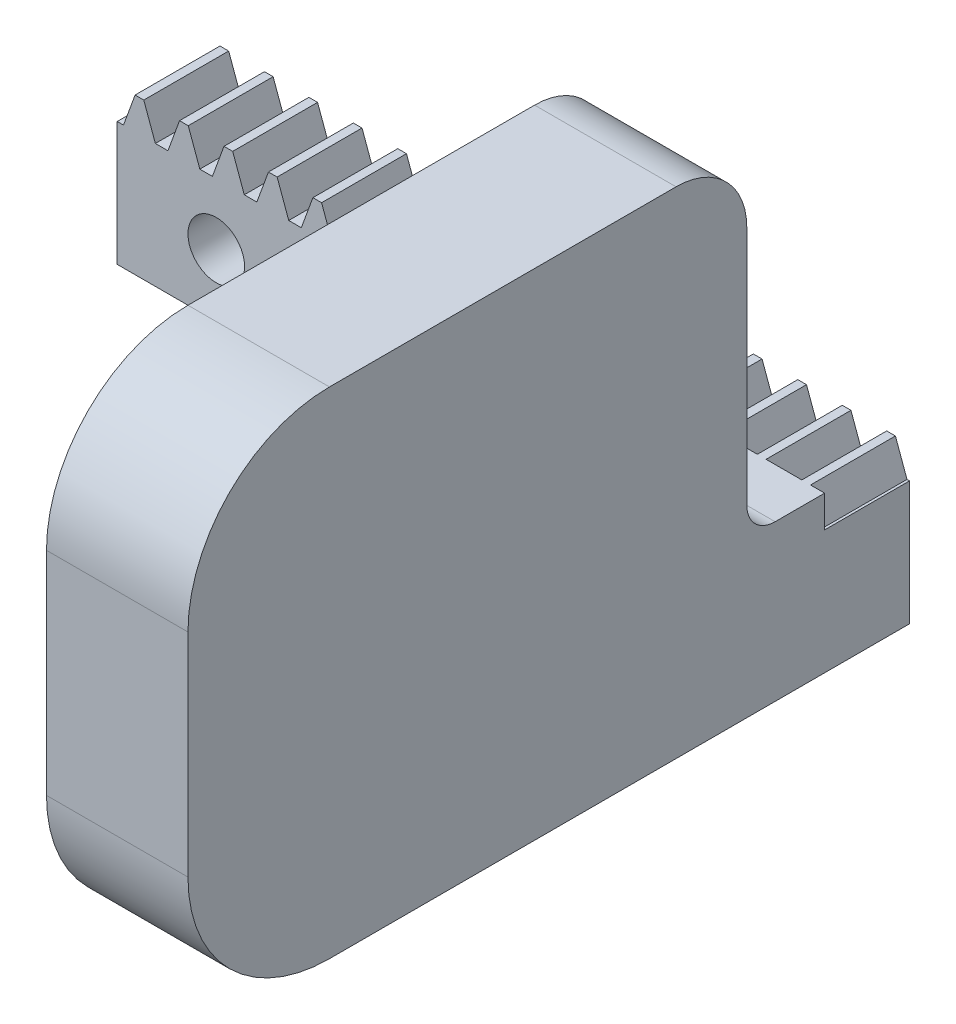
SolidWorks part; units mm, degrees
extrude "Blank" add sketch "BlankSke" against normal blind 6
sketch "BlankSke" plane through (0, 0, 0) normal (0, 0, 1) x (1, 0, 0)
  line L1 (0, 0) -> (50, 0)
  line L2 (0, 0) -> (0, 11)
  line L3 (0, 11) -> (50, 11)
  line L4 (50, 0) -> (50, 11)
  dimension "Length" = 50
ref_plane "Plane1" through (0, 0, 0) normal (0, 0, 1) x (1, 0, 0)
ref_plane "Plane2" through (0, 0, 0) normal (0, 1, 0) x (1, 0, 0)
ref_plane "Plane3" through (0, 0, 0) normal (1, 0, 0) x (0, 0, -1)
sketch "HoldingSke" plane through (0, 0, 0) normal (0, 1, 0) x (1, 0, 0)
  line L0 (0, 0) -> (0.1392, 0.9903)
  line L1 (-15, 0) -> (100, 0) construction
  line L2 (0, 0) -> (-2.1039, 2.3779)
  line L3 (0, 0) -> (-11.863, 4.5341)
  line L4 (0, 0) -> (8.2587, 2.5249)
  line L5 (0, 0) -> (-23.7986, -8.8762)
  line L6 (0, 0) -> (-10.5278, -7.1032)
  line L9 (-71.009, 38.7566) -> (-24.0243, 55.8576)
  line L10 (-76.2, 3.3779) -> (-66.2, 3.3779)
  line L11 (0, 0) -> (-6, 0)
  line L12 (-76.2, 101.6) -> (-76.162, 101.6)
  line L13 (24.9733, 27.94) -> (52.9518, 28.4284)
  line L14 (24.9733, 27.94) -> (24.9743, 27.94)
  line L15 (24.9733, 27.94) -> (100.4006, 29.5858)
  circle A0 centre (0, 0) radius 19.05
  circle A1 centre (0, 0) radius 5
  circle A2 centre (0, 0) radius 12.7
  dimension "Num_teeth" = 17
  dimension "Width" = 6
  dimension "Length" = 50
  dimension "Pitch_height" = 10
sketch "TooCutSkeIll" plane through (0, 0, 0) normal (0, 0, 1) x (1, 0, 0)
  line L0 (-1.2538, 10.9737) -> (-0.5045, 8.9152)
  line L1 (-0.2687, 8.75) -> (0.2687, 8.75)
  line L2 (0.5045, 8.9152) -> (1.2538, 10.9737)
  line L3 (50, 11) -> (0, 11) construction
  line L4 (0, 0) -> (0, 64.897) construction
  line L5 (-13.208, 10) -> (12.954, 10) construction
  line L6 (0, 0) -> (50, 0) construction
  line L7 (0.8994, 10) -> (0.8994, 48.7463) construction
  line L8 (-0.8994, 10) -> (-0.8994, 48.7463) construction
  line L9 (1.2914, 11) -> (1.2914, 11.0254)
  line L10 (-1.2914, 11) -> (-1.2914, 11.0254)
  line L11 (-1.2914, 11.0254) -> (1.2914, 11.0254)
  arc A0 (0.2687, 8.75) -> (0.5045, 8.9152) centre (0.2687, 9.001) ccw
  arc A1 (-0.5045, 8.9152) -> (-0.2687, 8.75) centre (-0.2687, 9.001) ccw
  arc A2 (1.2914, 11) -> (1.2538, 10.9737) centre (1.2914, 10.96) ccw
  arc A3 (-1.2538, 10.9737) -> (-1.2914, 11) centre (-1.2914, 10.96) ccw
  dimension "Addendum_plus" = 1.0254
  dimension "Pitch_height" = 10
  dimension "Pressure_angle" = 20
  dimension "Gap_width" = 1.7988
  dimension "Dedendum" = 1.25
extrude "ToothCutIll" [suppressed] cut sketch "TooCutSkeIll" against normal through all
sketch "TooCutSkeSim" plane through (0, 0, 0) normal (0, 0, 1) x (1, 0, 0)
  line L0 (0.4444, 8.75) -> (-0.4444, 8.75)
  line L1 (1.2726, 11.0254) -> (0.4444, 8.75)
  line L2 (0, 17.4625) -> (0, 53.467) construction
  line L3 (1.2726, 11.0254) -> (-1.2726, 11.0254)
  line L6 (-1.2726, 11.0254) -> (-0.4444, 8.75)
  line L9 (-0.8994, 10) -> (0.8994, 10) construction
  line L10 (0, 0) -> (50, 0) construction
  line L11 (0.8994, 10) -> (0.8994, 53.467) construction
  line L12 (-0.8994, 10) -> (-0.8994, 53.467) construction
  dimension "Addendum_plus" = 1.0254
  dimension "Pitch_height" = 10
  dimension "Pressure_angle" = 20
  dimension "Gap_width" = 1.7988
  dimension "Dedendum" = 1.25
extrude "ToothCutSim" cut sketch "TooCutSkeSim" against normal through all
pattern_linear "TeethCuts" count 17 spacing 3.1416 along (1, 0, 0) of "ToothCutIll", "ToothCutSim"
sketch "Sketch1" plane through (0, 0, 0) normal (0, 0, 1) x (1, 0, 0)
  line L1 (50, 0) -> (40, 0)
  line L2 (50, 0) -> (50, 35)
  line L3 (50, 35) -> (40, 35)
  line L4 (40, 0) -> (40, 35)
  dimension "D1" = 35
  dimension "D2" = 10
extrude "Boss-Extrude1" add sketch "Sketch1" along normal blind 45
fillet "Fillet1" radius 10 2 edges at (45, 0, 45) (45, 35, 45)
sketch "Sketch2" plane through (0, 0, 0) normal (0, 0, 1) x (1, 0, 0)
  line L0 (0, 8.75) -> (0, 0) construction
  line L1 (0, 4.375) -> (9, 4.375) construction
  line L2 (7, 8.1846) -> (7, 0) construction
  line L3 (0, 0) -> (40, 0) construction
  line L4 (40, 9.8387) -> (40, 0) construction
  line L5 (39.5773, 11) -> (38.9625, 11) construction
  circle A0 centre (7, 4.375) radius 2
  circle A1 centre (32, 4.375) radius 2
  dimension "D1" = 7
  dimension "D3" = 4
  dimension "D4" = 0.4227
  dimension "D2" = 25
  dimension "D5" = 1.1613
  dimension "D6" = 6.625
extrude "Cut-Extrude1" cut sketch "Sketch2" against normal blind 25
ref_axis "Axis1" through (50, 0, -6) along (-1, 0, 0)
sketch "Sketch3" plane through (0, 0, -6) normal (0, 0, -1) x (-1, 0, 0)
  circle A2 centre (-7, 4.375) radius 2 construction
  circle A3 centre (-32, 4.375) radius 2 construction
  circle A4 centre (-7, 4.375) radius 2
  circle A5 centre (-32, 4.375) radius 2
  circle A6 centre (-32, 4.375) radius 3
  circle A7 centre (-7, 4.375) radius 3
  dimension "D1" = 1
extrude "Boss-Extrude2" [suppressed] add sketch "Sketch3" along normal blind 4
sketch "Sketch4" plane through (40, 0, 0) normal (-1, 0, 0) x (0, 0, 1)
  line L1 (0, 11) -> (5.5, 11)
  line L2 (0, 11) -> (0, 41)
  line L3 (0, 41) -> (5.5, 41)
  line L4 (5.5, 11) -> (5.5, 41)
  dimension "D1" = 5.5
  dimension "D2" = 30
extrude "Cut-Extrude2" cut sketch "Sketch4" against normal blind 10
fillet "Fillet3" radius 2 1 edges at (45, 11, 5.5)
fillet "Fillet4" radius 5 1 edges at (45, 35, 5.5)
equation "' \"Module@HoldingSke\" = 6.35"
equation "' \"Num_teeth@HoldingSke\" = 12"
equation "' \"Ap@HoldingSke\" =  20"
equation "' \"Ap@HoldingSke\" = 20"
equation "' \"Width@HoldingSke\" = 0.25 * 25.4"
equation "' \"Show_teeth@HoldingSke\" = 500"
equation "' \"Backlash@HoldingSke\" = 0.009 * 25.4"
equation "' \"Addendum_fac@HoldingSke\" = 1.0"
equation "' \"Dedendum_fac@HoldingSke\" = 1.25"
equation "' \"Dedendum_add@HoldingSke\" = 0.00005 * 25.4"
equation "' \"Clearance_fac@HoldingSke\" = 0.25"
equation "' \"Pitch_height@HoldingSke\" = 1 * 25.4"
equation "' \"Length@HoldingSke\" = 4.71 * 25.4"
equation "\"Pitch@HoldingSke\" = 1 / \"Module@HoldingSke\""
equation "\"MPH@HoldingSke\" = \"Dedendum_fac@HoldingSke\" / \"Pitch@HoldingSke\" + 2 * \"Dedendum_add@HoldingSke\" + 0.002 * 25.4"
equation "\"MPH@HoldingSke\" = ((sgn( \"MPH@HoldingSke\" - \"Pitch_height@HoldingSke\")+1)*( \"MPH@HoldingSke\" - \"Pitch_height@HoldingSke\"))/2 + \"Pitch_height@HoldingSke\""
equation "\"Blank_height@BlankSke\" = \"Pitch_height@HoldingSke\" + \"Addendum_fac@HoldingSke\"  / \"Pitch@HoldingSke\" "
equation "\"Length@BlankSke\" =  \"Length@HoldingSke\""
equation "\"Face_width@Blank\" = \"Width@HoldingSke\""
equation "\"Pressure_angle@TooCutSkeIll\" = \"Ap@HoldingSke\""
equation "\"Addendum_plus@TooCutSkeIll\" =  \"Addendum_fac@HoldingSke\"  / \"Pitch@HoldingSke\" + 0.001 *25.4"
equation "\"Dedendum@TooCutSkeIll\" = \"Dedendum_fac@HoldingSke\"  / \"Pitch@HoldingSke\""
equation "\"Pitch_height@TooCutSkeIll\" =  \"MPH@HoldingSke\""
equation "\"Gap_width@TooCutSkeIll\" = 3.14159265 / 2 / \"Pitch@HoldingSke\" + 6 * \"Backlash@HoldingSke\""
equation "\"Pressure_angle@TooCutSkeSim\" = \"Ap@HoldingSke\""
equation "\"Addendum_plus@TooCutSkeSim\" =  \"Addendum_fac@HoldingSke\"  / \"Pitch@HoldingSke\" + 0.001 * 25.4"
equation "\"Dedendum@TooCutSkeSim\" = \"Dedendum_fac@HoldingSke\"  / \"Pitch@HoldingSke\""
equation "\"Pitch_height@TooCutSkeSim\" =  \"MPH@HoldingSke\""
equation "\"Gap_width@TooCutSkeSim\" = 3.14159265 / 2 / \"Pitch@HoldingSke\" + 6 * \"Backlash@HoldingSke\""
equation "\"Root_fillet@TooCutSkeIll\" = \"Clearance_fac@HoldingSke\" / \"Pitch@HoldingSke\" + \"Dedendum_add@HoldingSke\""
equation "\"Break_rad@TooCutSkeIll\" = 0.02 / \"Pitch@HoldingSke\" * 2"
equation "\"Linear_pitch@TeethCuts\" = 3.14159265 / \"Pitch@HoldingSke\""
equation "\"Num_teeth@HoldingSke\" = int( ( \"Length@HoldingSke\" + 0 ) / (3.14159265 / \"Pitch@HoldingSke\")) + 0.9999  + 1"
equation " \"Num_teeth@TeethCuts\" = int( \"Show_teeth@HoldingSke\" ) + 1"
equation " \"Num_teeth@TeethCuts\" = ((sgn( \"Num_teeth@TeethCuts\" - \"Num_teeth@HoldingSke\" )-1)*( \"Num_teeth@TeethCuts\" - \"Num_teeth@HoldingSke\" ))/-2+ \"Num_teeth@HoldingSke\""
equation " \"Num_teeth@TeethCuts\" = ((sgn( \"Num_teeth@TeethCuts\" - 2.0)+1)*( \"Num_teeth@TeethCuts\" - 2.0))/2 +2.0"
